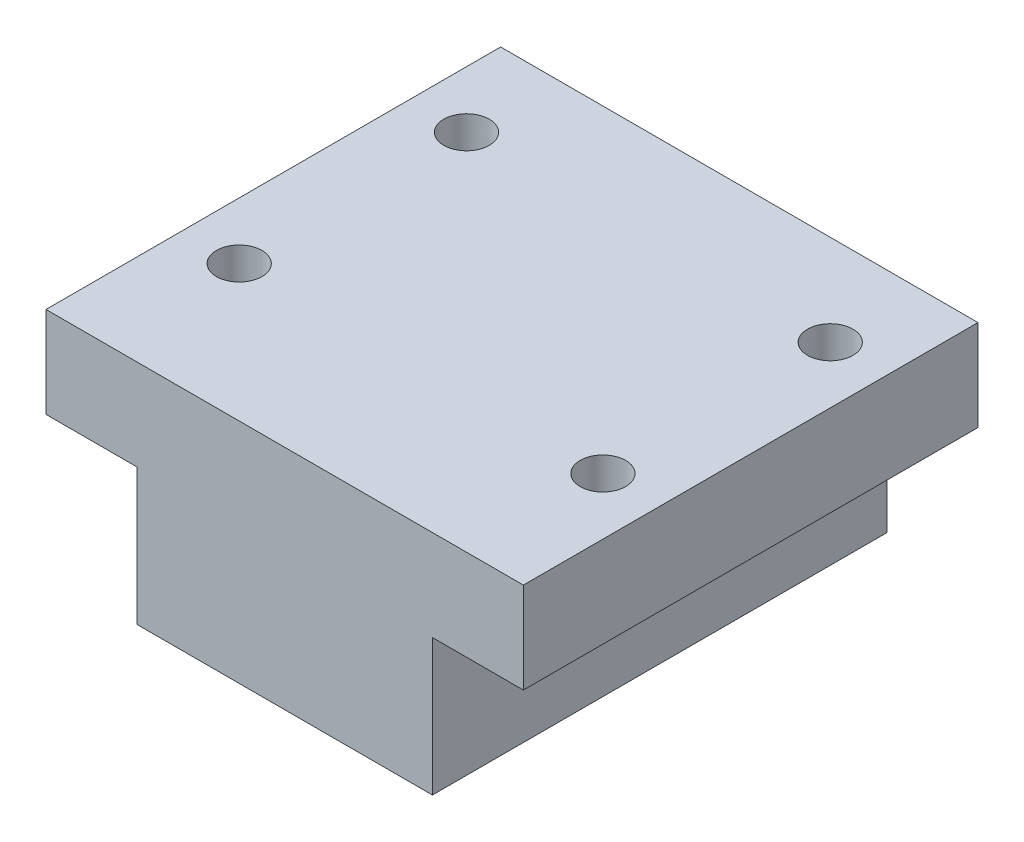
SolidWorks part; units mm, degrees
ref_plane "Front Plane" through (0, 0, 0) normal (0, 0, 1) x (1, 0, 0)
ref_plane "Top Plane" through (0, 0, 0) normal (0, 1, 0) x (1, 0, 0)
ref_plane "Right Plane" through (0, 0, 0) normal (1, 0, 0) x (0, 0, -1)
sketch "Sketch1" plane through (0, 0, 0) normal (0, 0, 1) x (1, 0, 0)
  line L0 (13, -4) -> (21, -4)
  line L1 (-21, -4) -> (-13, -4)
  line L2 (-21, -4) -> (-21, 4)
  line L3 (-21, 4) -> (21, 4)
  line L4 (21, -4) -> (21, 4)
  line L5 (-21, -4) -> (21, 4) construction
  line L6 (-21, 4) -> (21, -4) construction
  line L8 (13, -4) -> (13, -16)
  line L9 (13, -16) -> (-13, -16)
  line L10 (-13, -4) -> (-13, -16)
  point P0 (0, 0)
  dimension "D1" = 42
  dimension "D2" = 8
  dimension "D3" = 12
  dimension "D4" = 26
  dimension "D5" = 8
extrude "Boss-Extrude1" add sketch "Sketch1" along normal mid plane 40
sketch "Sketch2" plane through (0, 4, 0) normal (0, 1, 0) x (1, 0, 0)
  line L0 (-16, -8) -> (16, -8) construction
  line L1 (16, -8) -> (16, 12) construction
  line L2 (16, 12) -> (-16, 12) construction
  line L3 (-16, 12) -> (-16, -8) construction
  line L4 (21, -20) -> (-21, -20) construction
  circle A0 centre (-16, 12) radius 2
  circle A1 centre (16, 12) radius 2
  circle A2 centre (-16, -8) radius 2
  circle A3 centre (16, -8) radius 2
  dimension "D1" = 4
  dimension "D2" = 4
  dimension "D3" = 4
  dimension "D4" = 4
  dimension "D5" = 32
  dimension "D6" = 20
  dimension "D7" = 12
extrude "Cut-Extrude1" cut sketch "Sketch2" against normal blind 40
sketch "Sketch4" plane through (0, -16, 0) normal (0, -1, 0) x (1, 0, 0)
  line L0 (-13, -20) -> (13, -20) construction
  line L2 (0, 0) -> (0, -4.5) construction
  circle A0 centre (0, -4.5) radius 5.5
  point P7 (0, 0)
  dimension "D1" = 15.5
  dimension "D2" = 11
extrude "Cut-Extrude2" cut sketch "Sketch4" against normal blind 1.75
